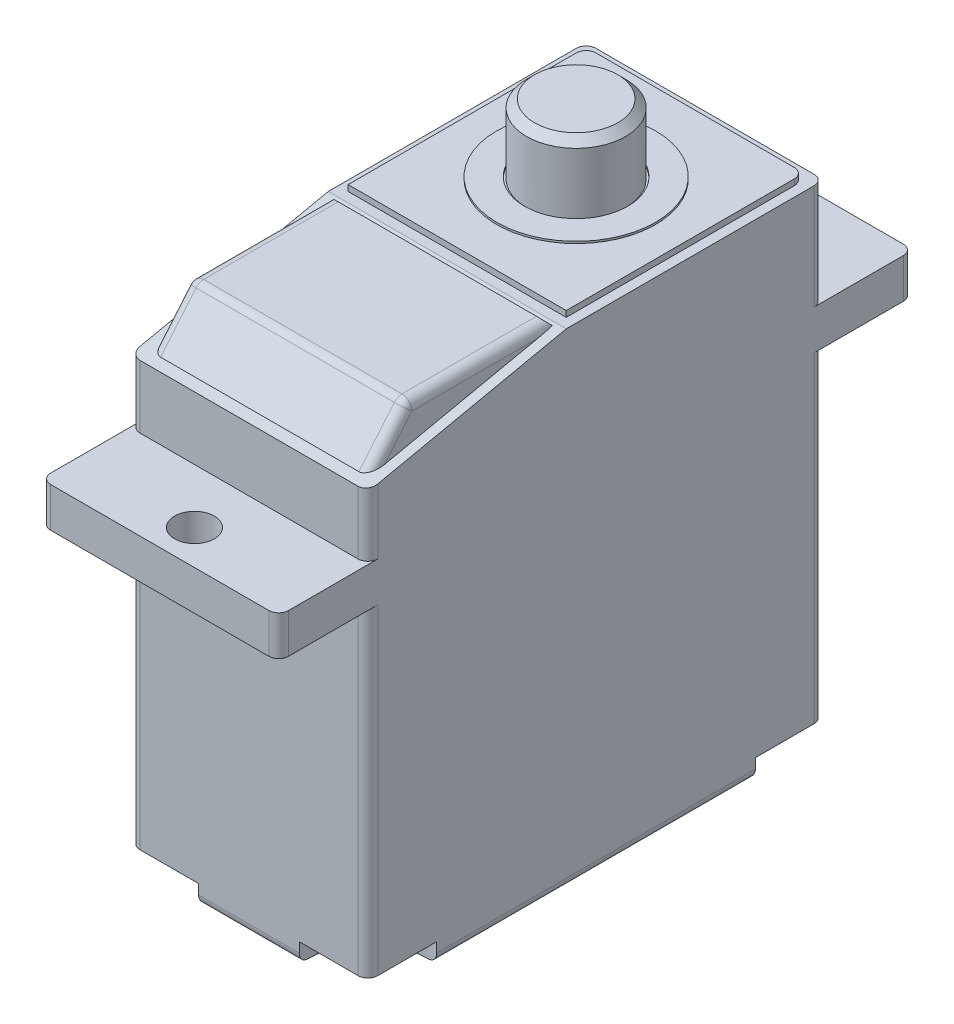
SolidWorks part; units mm, degrees
material "ABS generico"
ref_plane "Piano frontale" through (0, 0, 0) normal (0, 0, 1) x (1, 0, 0)
ref_plane "Piano superiore" through (0, 0, 0) normal (0, 1, 0) x (1, 0, 0)
ref_plane "Piano destro" through (0, 0, 0) normal (1, 0, 0) x (0, 0, -1)
sketch "Schizzo3" plane through (0, 0, 0) normal (0, 1, 0) x (1, 0, 0)
  line L1 (-6, -11.5) -> (6, -11.5)
  line L2 (-6, -11.5) -> (-6, 11.5)
  line L3 (-6, 11.5) -> (6, 11.5)
  line L4 (6, -11.5) -> (6, 11.5)
  line L5 (-6, -11.5) -> (6, 11.5) construction
  line L6 (-6, 11.5) -> (6, -11.5) construction
  point P0 (0, 0)
  dimension "D1" = 12
  dimension "D2" = 23
extrude "Estrusione-Estrusione2" add sketch "Schizzo3" along normal blind 24.5
ref_plane "Piano1" through (0, 17.2, 0) normal (0, 1, 0) x (1, 0, 0)
sketch "Schizzo4" plane through (0, 17.2, 0) normal (0, 1, 0) x (1, 0, 0)
  line L1 (-6, 16) -> (6, 16)
  line L2 (-6, 16) -> (-6, -16)
  line L3 (-6, -16) -> (6, -16)
  line L4 (6, 16) -> (6, -16)
  line L5 (-6, 16) -> (6, -16) construction
  line L6 (-6, -16) -> (6, 16) construction
  point P0 (0, 0)
  dimension "D1" = 12
  dimension "D2" = 32
extrude "Estrusione-Estrusione3" add sketch "Schizzo4" along normal blind 2
sketch "Schizzo5" plane through (0, 24.5, 0) normal (0, 1, 0) x (1, 0, 0)
  line L0 (-6, -11.5) -> (-6, -1.5) construction
  line L1 (-6, 11.5) -> (-6, -11.5) construction
  line L2 (-6, -1.5) -> (6, -1.5) construction
  line L3 (6, -11.5) -> (6, 11.5) construction
  dimension "D1" = 10
ref_plane "Piano2" through (0, 23.746, 5.0474) normal (0, 0.9781, 0.2079) x (1, 0, 0)
sketch "Schizzo6" plane through (0, 23.746, 5.0474) normal (0, 0.9781, 0.2079) x (1, 0, 0)
  line L1 (-6.5, -10) -> (6.5, -10)
  line L2 (-6.5, -10) -> (-6.5, 10)
  line L3 (-6.5, 10) -> (6.5, 10)
  line L4 (6.5, -10) -> (6.5, 10)
  line L5 (-6.5, -10) -> (6.5, 10) construction
  line L6 (-6.5, 10) -> (6.5, -10) construction
  point P0 (0, 0)
  dimension "D1" = 20
  dimension "D2" = 13
extrude "Taglio-Estrusione1" cut sketch "Schizzo6" along normal through all
sketch "Schizzo7" plane through (0, 24.5, 0) normal (0, 1, 0) x (1, 0, 0)
  line L0 (-6, 11.5) -> (6, -1.5) construction
  line L2 (-5.5, -1) -> (5.5, -1)
  line L3 (-5.5, -1) -> (-5.5, 11)
  line L4 (-5.5, 11) -> (5.5, 11)
  line L5 (5.5, -1) -> (5.5, 11)
  line L6 (-5.5, -1) -> (5.5, 11) construction
  line L7 (-5.5, 11) -> (5.5, -1) construction
  point P4 (0, 5)
  dimension "D1" = 11
  dimension "D2" = 12
extrude "Estrusione-Estrusione4" add sketch "Schizzo7" along normal blind 0.3 contours L4 L5 L2 L3
sketch "Schizzo8" plane through (0, 24.8, 0) normal (0, 1, 0) x (1, 0, 0)
  line L1 (-5.5, -1) -> (5.5, -1)
  line L2 (-5.5, -1) -> (-5.5, -2)
  line L3 (-5.5, -2) -> (5.5, -2)
  line L4 (5.5, -1) -> (5.5, -2)
  line L5 (-5.5, -1) -> (5.5, -2) construction
  line L6 (-5.5, -2) -> (5.5, -1) construction
  line L7 (-5.5, -2) -> (5.5, -2)
  line L8 (-5.5, -2) -> (-5.5, -9)
  line L9 (-5.5, -9) -> (5.5, -9)
  line L10 (5.5, -2) -> (5.5, -9)
  line L11 (-5.5, -2) -> (5.5, -9) construction
  line L12 (-5.5, -9) -> (5.5, -2) construction
  point P5 (0, -1.5)
  point P8 (0, -5.5)
  dimension "D1" = 11
  dimension "D2" = 1
  dimension "D3" = 7
extrude "Estrusione-Estrusione5" add sketch "Schizzo8" against normal up to next contours L10 L3 L8 L9 region at (0, 24.8, 5.5)
chamfer "Smusso1" distance 2 angle 38 1 edges at (0, 22.9058, 9) first distance on face at (0, 23.6498, 5.5)
chamfer "Smusso2" distance 0.4 angle 45 1 edges at (0, 24.3937, 2) first distance on face at (0, 24.5969, 2)
fillet "Raccordo5" radius 0.5 16 edges at (0, 0, -11.5) (-6, 0, 0) (0, 0, 11.5) (6, 0, 0) (6, 20.7872, 11.5) (-6, 20.7872, 11.5) (6, 21.85, -11.5) (-6, 21.85, -11.5) (6, 8.6, -11.5) (-6, 8.6, -11.5) (-6, 8.6, 11.5) (6, 8.6, 11.5) (-6, 18.2, 16) (6, 18.2, 16) (-6, 18.2, -16) (6, 18.2, -16)
fillet "Raccordo6" radius 0.5 7 edges at (-5.5, 23.645, 9.9871) (-5.5, 24.8, 5.509) (0, 24.8, 9.018) (5.5, 23.645, 9.9871) (5.5, 24.8, 5.509) (5.5, 24.65, -11) (-5.5, 24.65, -11)
sketch "Schizzo9" plane through (0, 19.2, 0) normal (0, 1, 0) x (1, 0, 0)
  line L0 (0, 14.25) -> (0, -14.25) construction
  circle A0 centre (0, 14.25) radius 1
  circle A1 centre (0, -14.25) radius 1
  point P4 (0, 0)
  dimension "D2" = 2
  dimension "D3" = 2
  dimension "D1" = 28.5
extrude "Taglio-Estrusione2" cut sketch "Schizzo9" against normal up to next
sketch "Schizzo10" plane through (0, 24.8, 0) normal (0, 1, 0) x (1, 0, 0)
  line L0 (0, -1) -> (0, 11) construction
  line L1 (-5.5, -1) -> (5.5, -1) construction
  line L2 (-5, 11) -> (5, 11) construction
  circle A0 centre (0, 5) radius 2.5
  dimension "D1" = 5
extrude "Estrusione-Estrusione6" add sketch "Schizzo10" along normal blind 3.5 and the other way blind 1 contours A0
chamfer "Smusso3" distance 0.4 angle 45 1 edges at (0, 28.3, -2.5)
sketch "Schizzo11" plane through (0, 24.8, 0) normal (0, 1, 0) x (1, 0, 0)
  circle A0 centre (0, 5) radius 4
  circle A1 centre (0, 5) radius 2.6
  dimension "D1" = 8
  dimension "D2" = 5.2
extrude "Estrusione-Estrusione7" add sketch "Schizzo11" along normal blind 0.1
sketch "Schizzo13" plane through (0, 0, 0) normal (0, -1, 0) x (1, 0, 0)
  circle A0 centre (5.5, 11) radius 3
  circle A1 centre (-5.5, 11) radius 3
  circle A2 centre (-5.5, -11) radius 3
  circle A3 centre (5.5, -11) radius 3
  dimension "D1" = 6
  dimension "D2" = 6
  dimension "D3" = 6
  dimension "D4" = 6
extrude "Taglio-Estrusione3" cut sketch "Schizzo13" against normal blind 1
sketch "Schizzo15" plane through (0, 1, 0) normal (0, -1, 0) x (1, 0, 0)
  line L1 (-5.5, -11) -> (5.5, -11)
  line L2 (-5.5, -11) -> (-5.5, 11)
  line L3 (-5.5, 11) -> (5.5, 11)
  line L4 (5.5, -11) -> (5.5, 11)
sketch "Schizzo16" plane through (0, 0, -11.5) normal (0, 0, -1) x (-1, 0, 0)
  line L0 (0, 0) -> (0, 2) construction
  circle A0 centre (0, 2) radius 0.375
  circle A3 centre (0.8, 2) radius 0.375
  circle A4 centre (-0.8, 2) radius 0.375
  dimension "D2" = 0.75
  dimension "D1" = 2
  dimension "D3" = 2
  dimension "D4" = 2
extrude "Estrusione-Estrusione10" add sketch "Schizzo16" along normal blind 2 contours A0 | A4 | A3 region at (0, 2, -11.5) region at (0.8, 2, -11.5)
